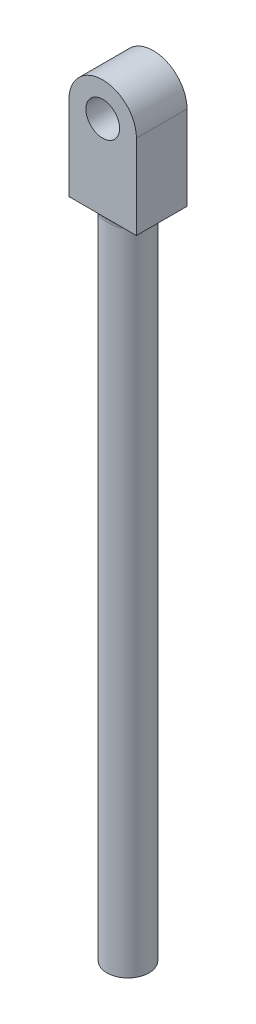
SolidWorks part; units mm, degrees
ref_plane "Front Plane" through (0, 0, 0) normal (0, 0, 1) x (1, 0, 0)
ref_plane "Top Plane" through (0, 0, 0) normal (0, 1, 0) x (1, 0, 0)
ref_plane "Right Plane" through (0, 0, 0) normal (1, 0, 0) x (0, 0, -1)
sketch "Sketch1" plane through (0, 0, 0) normal (0, 1, 0) x (1, 0, 0)
  circle A0 centre (0, 0) radius 2.5
  dimension "D1" = 5
extrude "Boss-Extrude1" add sketch "Sketch1" along normal blind 78
sketch "Sketch3" plane through (0, 0, 0) normal (0, 0, 1) x (1, 0, 0)
  line L0 (4, 78) -> (-4, 78)
  line L1 (4, 78) -> (4, 88)
  line L2 (-4, 78) -> (-4, 88)
  line L4 (2.5, 78) -> (-2.5, 78) construction
  circle A0 centre (0, 88) radius 2
  arc A1 (4, 88) -> (-4, 88) centre (0, 88) ccw
  point P7 (0, 78)
  dimension "D3" = 4
  dimension "D1" = 8
  dimension "D2" = 10
extrude "Boss-Extrude2" add sketch "Sketch3" along normal mid plane 6
fillet "Fillet1" radius 1 1 edges at (0, 78, 2.5)
